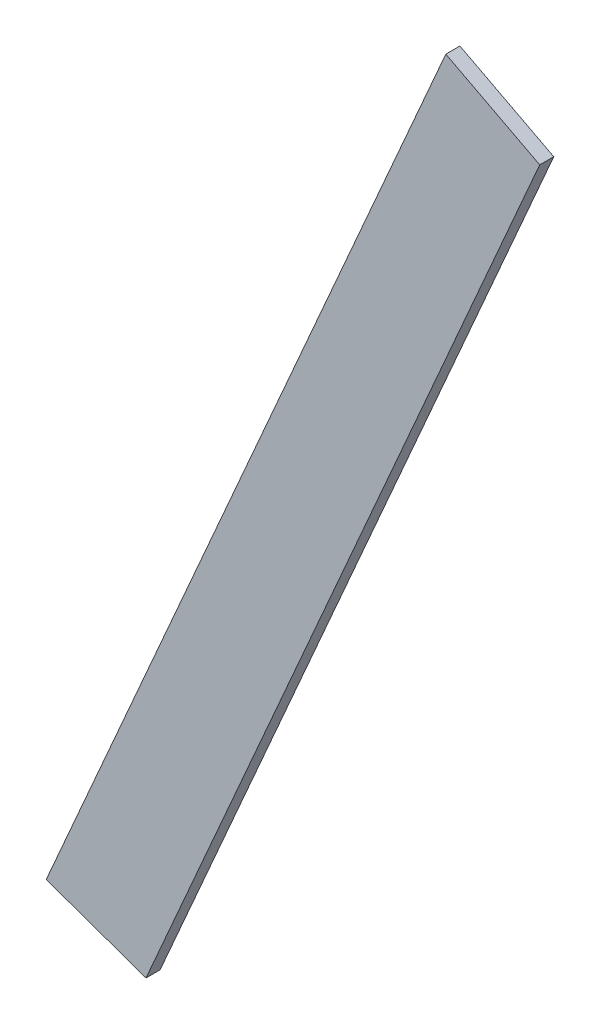
SolidWorks part; units mm, degrees
ref_plane "Front Plane" through (0, 0, 0) normal (0, 0, 1) x (1, 0, 0)
ref_plane "Top Plane" through (0, 0, 0) normal (0, 1, 0) x (1, 0, 0)
ref_plane "Right Plane" through (0, 0, 0) normal (1, 0, 0) x (0, 0, -1)
sketch "Sketch1" plane through (0, 0, 0) normal (0, 0, 1) x (1, 0, 0)
  line L0 (31.6098, -12.2781) -> (17.4369, -7.2514)
  line L2 (17.4369, -7.2514) -> (74.1892, 122.6416)
  line L4 (31.6098, -12.2781) -> (87.5222, 115.6925)
  line L5 (87.5222, 115.6925) -> (74.1892, 122.6416)
  line L6 (148.1281, 84.1053) -> (-29.2287, 176.542) construction
  line L7 (-92.305, 31.6708) -> (96.1906, -35.183) construction
  dimension "D1" = 15
extrude "Boss-Extrude1" add sketch "Sketch1" along normal blind 2
ref_plane "Plane1" through (24.1748, -10.5624, 0) normal (0.9164, -0.4004, 0) x (0, 0, -1)
